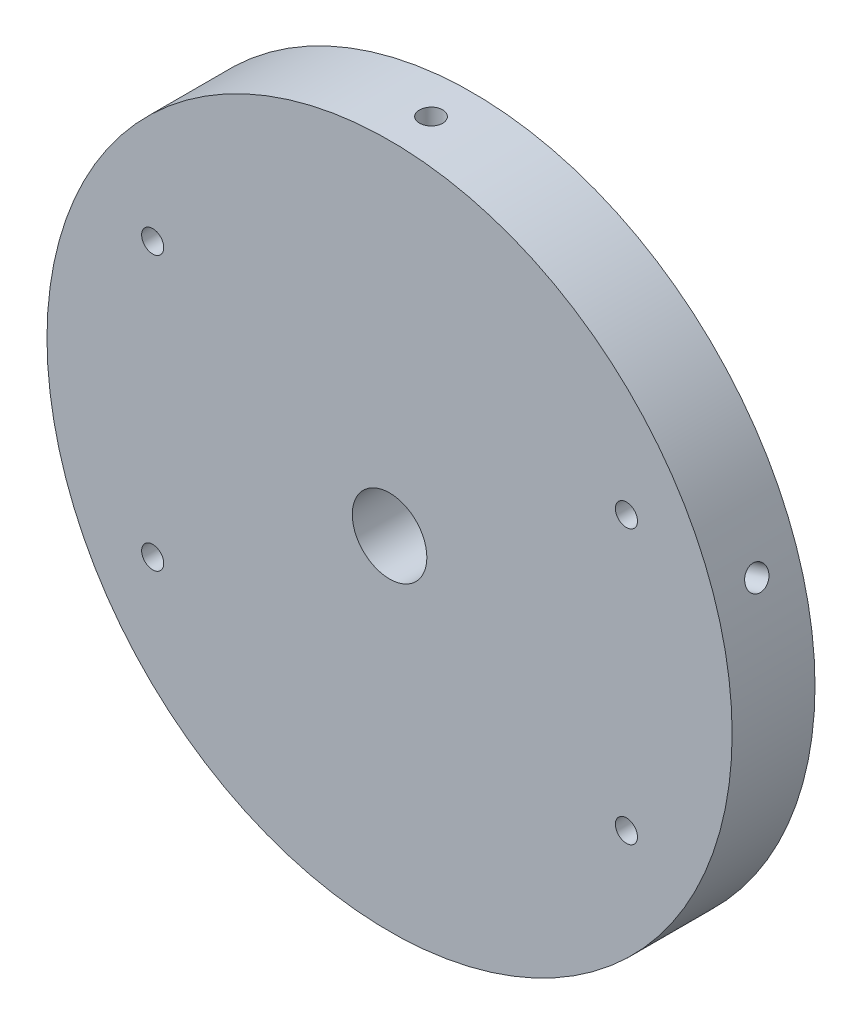
SolidWorks part; units mm, degrees
material "Polyetheretherketone (PEEK)"
ref_plane "Front Plane" through (0, 0, 0) normal (0, 0, 1) x (1, 0, 0)
ref_plane "Top Plane" through (0, 0, 0) normal (0, 1, 0) x (1, 0, 0)
ref_plane "Right Plane" through (0, 0, 0) normal (1, 0, 0) x (0, 0, -1)
sketch "Sketch1" plane through (0, 0, 0) normal (0, 0, 1) x (1, 0, 0)
  circle A0 centre (0, 0) radius 62
  dimension "D1" = 124
extrude "Boss-Extrude1" add sketch "Sketch1" along normal blind 15 contours A0
sketch "Sketch7" plane through (0, 0, 0) normal (0, 0, -1) x (-1, 0, 0)
  line L0 (0, 0) -> (-42.8683, 24.75) construction
  line L2 (0, 0) -> (-42.8683, -24.75) construction
  line L3 (-42.8683, -24.75) -> (-42.8683, 24.75) construction
  line L5 (0, 8.25) -> (0, -8.25) construction
  point P0 (-42.8683, 24.75)
  point P2 (-42.8683, -24.75)
  point P20 (42.8683, -24.75)
  point P21 (42.8683, 24.75)
  dimension "D1" = 49.5
  dimension "D2" = 49.5
hole_wizard "Ø4.0 (4) Diameter Hole1" positions "Sketch7" profile "Sketch8" hole size "Ø4.0" standard "ISO" end condition up to next
sketch "Sketch8" plane through (42.8683, 24.75, 0) normal (1, 0, 0) x (0, 1, 0)
  line L0 (0, 0) -> (0, 15)
  line L1 (0, 15) -> (2, 15)
  line L2 (2, 15) -> (2, 0)
  line L5 (2, 0) -> (0, 0)
  line L11 (0, -6.35) -> (0, 107.95) construction
  dimension "Thru Hole Dia." = 4
  dimension "Thru Hole Depth" = 15
sketch "Sketch9" plane through (0, 0, 0) normal (0, 0, -1) x (-1, 0, 0)
  point P0 (0, 0)
hole_wizard "M12 Clearance Hole1" positions "Sketch9" profile "Sketch10" hole size "M12" standard "ISO" end condition up to next
sketch "Sketch10" plane through (0, 0, 0) normal (1, 0, 0) x (0, 1, 0)
  line L0 (0, 0) -> (0, 15)
  line L1 (0, 15) -> (6.75, 15)
  line L2 (6.75, 15) -> (6.75, 0)
  line L5 (6.75, 0) -> (0, 0)
  line L11 (0, -6.35) -> (0, 107.95) construction
  dimension "Thru Hole Dia." = 13.5
  dimension "Thru Hole Depth" = 15
hole_wizard "M5 Tapped Hole1" positions "3DSketch1" profile "Sketch11" tap size "M5" standard "ISO"
sketch3d "3DSketch1"
  line L1 (0, 62, 7.5) -> (-58.9655, 19.1591, 7.5) construction
  line L2 (-58.9655, 19.1591, 7.5) -> (-36.4427, -50.1591, 7.5) construction
  line L3 (-36.4427, -50.1591, 7.5) -> (36.4427, -50.1591, 7.5) construction
  line L4 (36.4427, -50.1591, 7.5) -> (58.9655, 19.1591, 7.5) construction
  line L5 (58.9655, 19.1591, 7.5) -> (0, 62, 7.5) construction
  circle A0 centre (0, 0, 7.5) radius 62 construction
  circle A1 centre (0, 0, 0) radius 62 construction
  point P0 (0, 62, 7.5)
  point P2 (58.9655, 19.1591, 7.5)
  point P4 (36.4427, -50.1591, 7.5)
  point P6 (-36.4427, -50.1591, 7.5)
  point P8 (-58.9655, 19.1591, 7.5)
  point P13 (0, 0, 69.5)
  point P19 (0, 0, 62)
  dimension "D1" = 7.5
sketch "Sketch11" plane through (0, 62, 7.5) normal (1, 0, 0) x (0, 0, 1)
  line L0 (0, 0) -> (0, 13.6618)
  line L1 (0, 13.6618) -> (2.1, 12.4)
  line L2 (2.1, 12.4) -> (2.1, 0)
  line L5 (2.1, 0) -> (0, 0)
  line L10 (0, 13.6618) -> (-2.1, 12.4) construction
  line L11 (0, -6.35) -> (0, 107.95) construction
  dimension "Tap Drill Dia." = 4.2
  dimension "Tap Drill Depth" = 12.4
  dimension "Drill Angle" = 118
cosmetic thread "Hole Thread1" parameters "D1"=10, "D2"=5
cosmetic thread "Hole Thread2" parameters "D1"=10, "D2"=5
cosmetic thread "Hole Thread3" parameters "D1"=10, "D2"=5
cosmetic thread "Hole Thread4" parameters "D1"=10, "D2"=5
cosmetic thread "Hole Thread5" parameters "D1"=10, "D2"=5
